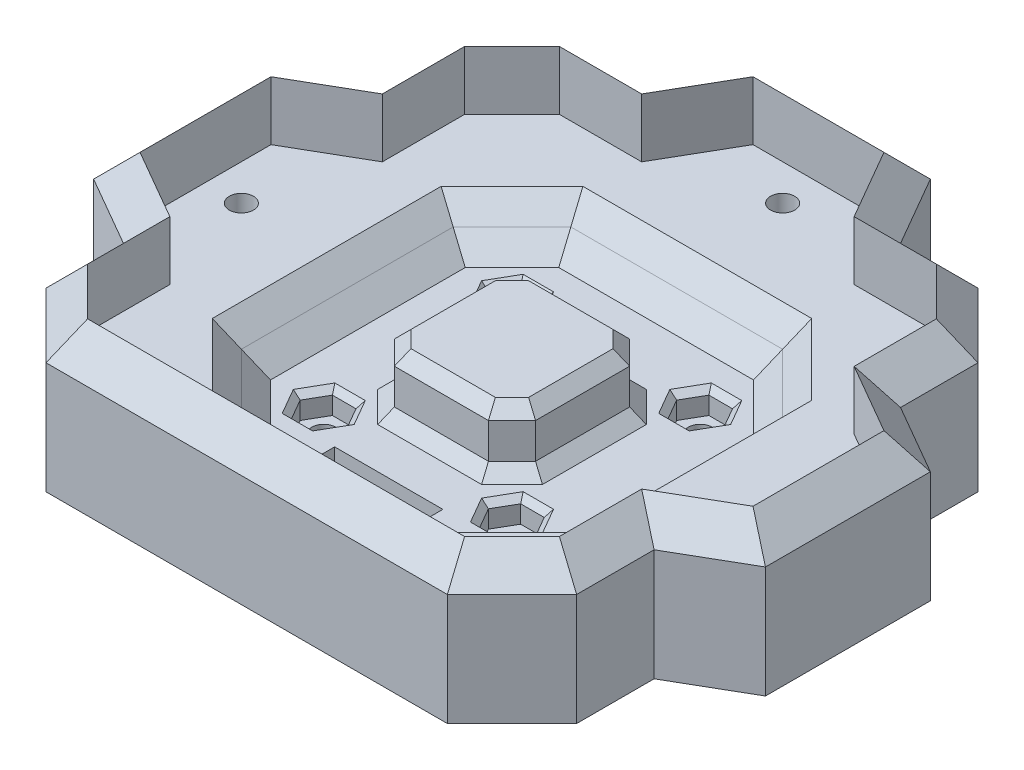
SolidWorks part; units mm, degrees
material "ABS"
ref_plane "Front Plane" through (0, 0, 0) normal (0, 0, 1) x (1, 0, 0)
ref_plane "Top Plane" through (0, 0, 0) normal (0, 1, 0) x (1, 0, 0)
ref_plane "Right Plane" through (0, 0, 0) normal (1, 0, 0) x (0, 0, -1)
sketch "Track Reference" plane through (0, 0, 0) normal (0, 1, 0) x (1, 0, 0)
  line L0 (-40, 32) -> (-32, 40)
  line L1 (-32, 40) -> (-18, 40)
  line L2 (-40, 32) -> (-40, 18)
  line L3 (-32, -40) -> (-5, -40)
  line L4 (40, 32) -> (40, 18)
  line L5 (-40, -32) -> (-32, -40)
  line L6 (32, -40) -> (40, -32)
  line L7 (32, 40) -> (40, 32)
  line L8 (-40, -18) -> (-52, -11.0718)
  line L9 (-52, -11.0718) -> (-52, 11.0718)
  line L10 (-52, 11.0718) -> (-40, 18)
  line L11 (-18, 40) -> (-11.0718, 52)
  line L12 (-11.0718, 52) -> (11.0718, 52)
  line L13 (11.0718, 52) -> (18, 40)
  line L14 (40, 18) -> (52, 11.0718)
  line L15 (52, 11.0718) -> (52, -11.0718)
  line L16 (52, -11.0718) -> (40, -18)
  line L17 (18, -40) -> (11.0718, -52)
  line L18 (11.0718, -52) -> (-11.0718, -52)
  line L19 (-11.0718, -52) -> (-18, -40)
  line L20 (-5, -27.65) -> (-5, -40)
  line L21 (-5, -27.65) -> (-9, -23.65)
  line L22 (-9, -23.65) -> (-9, -21.15)
  line L23 (-9, -21.15) -> (9, -21.15)
  line L24 (9, -21.15) -> (9, -23.65)
  line L25 (9, -23.65) -> (5, -27.65)
  line L26 (5, -27.65) -> (5, -40)
  line L27 (-40, 18) -> (-40, -18) construction
  line L28 (-40, -18) -> (-40, -32)
  line L29 (-18, 40) -> (18, 40) construction
  line L30 (18, 40) -> (32, 40)
  line L31 (40, 18) -> (40, -18) construction
  line L32 (40, -18) -> (40, -32)
  line L33 (-5, -40) -> (5, -40) construction
  line L34 (5, -40) -> (32, -40)
  circle A0 centre (-46, 0) radius 2.05
  circle A1 centre (0, 46) radius 2.05
  circle A2 centre (46, 0) radius 2.05
  circle A3 centre (0, -46) radius 2.05
  point P0 (-40, 40)
  point P1 (40, -40)
  point P2 (-40, -40)
  point P3 (40, 40)
  point P14 (-52, 0)
  point P22 (0, -21.15)
  point P23 (0, 0)
  point P44 (0, 0)
  dimension "D8" = 4.1
  dimension "D1" = 80
  dimension "D2" = 80
  dimension "D3" = 8
  dimension "D4" = 8
  dimension "D5" = 60
  dimension "D6" = 12
  dimension "D7" = 36
  dimension "D9" = 6
  dimension "D12" = 18
  dimension "D11" = 10
  dimension "D13" = 2.5
  dimension "D14" = 45
  dimension "D15" = 18.85
  dimension "D10" = 4
sketch "Sketch2" plane through (0, 0, 0) normal (0, 1, 0) x (1, 0, 0)
  line L127 (-5, -40.1) -> (5, -40.1)
  line L128 (-5, -45.1) -> (5, -45.1)
  line L129 (5, -45.1) -> (34.1125, -45.1)
  line L130 (34.1125, -45.1) -> (45.1, -34.1125)
  line L131 (45.1, -34.1125) -> (45.1, -20.9445)
  line L132 (45.1, -20.9445) -> (57.1, -14.0163)
  line L133 (57.1, -14.0163) -> (57.1, 14.0163)
  line L134 (57.1, 14.0163) -> (45.1, 20.9445)
  line L135 (45.1, 20.9445) -> (45.1, 34.1125)
  line L136 (45.1, 34.1125) -> (34.1125, 45.1)
  line L137 (34.1125, 45.1) -> (20.9445, 45.1)
  line L138 (20.9445, 45.1) -> (14.0163, 57.1)
  line L139 (14.0163, 57.1) -> (-14.0163, 57.1)
  line L140 (-14.0163, 57.1) -> (-20.9445, 45.1)
  line L141 (-20.9445, 45.1) -> (-34.1125, 45.1)
  line L142 (-34.1125, 45.1) -> (-45.1, 34.1125)
  line L143 (-45.1, 34.1125) -> (-45.1, 20.9445)
  line L144 (-45.1, 20.9445) -> (-57.1, 14.0163)
  line L145 (-57.1, 14.0163) -> (-57.1, -14.0163)
  line L146 (-57.1, -14.0163) -> (-45.1, -20.9445)
  line L147 (-45.1, -20.9445) -> (-45.1, -34.1125)
  line L148 (11.1295, 52.1) -> (-11.1295, 52.1)
  line L149 (18.0577, 40.1) -> (11.1295, 52.1)
  line L150 (32.0414, 40.1) -> (18.0577, 40.1)
  line L151 (40.1, 32.0414) -> (32.0414, 40.1)
  line L152 (40.1, 18.0577) -> (40.1, 32.0414)
  line L153 (52.1, 11.1295) -> (40.1, 18.0577)
  line L154 (52.1, -11.1295) -> (52.1, 11.1295)
  line L155 (40.1, -18.0577) -> (52.1, -11.1295)
  line L156 (40.1, -32.0414) -> (40.1, -18.0577)
  line L157 (32.0414, -40.1) -> (40.1, -32.0414)
  line L158 (5, -40.1) -> (32.0414, -40.1)
  line L159 (-32.0414, -40.1) -> (-5, -40.1)
  line L160 (-40.1, -32.0414) -> (-32.0414, -40.1)
  line L161 (-40.1, -18.0577) -> (-40.1, -32.0414)
  line L162 (-52.1, -11.1295) -> (-40.1, -18.0577)
  line L163 (-52.1, 11.1295) -> (-52.1, -11.1295)
  line L164 (-40.1, 18.0577) -> (-52.1, 11.1295)
  line L165 (-40.1, 32.0414) -> (-40.1, 18.0577)
  line L166 (-32.0414, 40.1) -> (-40.1, 32.0414)
  line L167 (-18.0577, 40.1) -> (-32.0414, 40.1)
  line L168 (-11.1295, 52.1) -> (-18.0577, 40.1)
  line L169 (11.1295, 52.1) -> (-11.1295, 52.1)
  line L170 (18.0577, 40.1) -> (11.1295, 52.1)
  line L171 (32.0414, 40.1) -> (18.0577, 40.1)
  line L172 (40.1, 32.0414) -> (32.0414, 40.1)
  line L173 (40.1, 18.0577) -> (40.1, 32.0414)
  line L174 (52.1, 11.1295) -> (40.1, 18.0577)
  line L175 (52.1, -11.1295) -> (52.1, 11.1295)
  line L176 (40.1, -18.0577) -> (52.1, -11.1295)
  line L177 (40.1, -32.0414) -> (40.1, -18.0577)
  line L178 (32.0414, -40.1) -> (40.1, -32.0414)
  line L179 (5, -40.1) -> (32.0414, -40.1)
  line L180 (-32.0414, -40.1) -> (-5, -40.1)
  line L181 (-40.1, -32.0414) -> (-32.0414, -40.1)
  line L182 (-40.1, -18.0577) -> (-40.1, -32.0414)
  line L183 (-52.1, -11.1295) -> (-40.1, -18.0577)
  line L184 (-52.1, 11.1295) -> (-52.1, -11.1295)
  line L185 (-40.1, 18.0577) -> (-52.1, 11.1295)
  line L186 (-40.1, 32.0414) -> (-40.1, 18.0577)
  line L187 (-32.0414, 40.1) -> (-40.1, 32.0414)
  line L188 (-18.0577, 40.1) -> (-32.0414, 40.1)
  line L189 (-11.1295, 52.1) -> (-18.0577, 40.1)
  line L190 (-45.1, -34.1125) -> (-34.1125, -45.1)
  line L191 (-34.1125, -45.1) -> (-5, -45.1)
  dimension "D1" = 0.1
  dimension "D2" = 5
extrude "Outer Walls Extrude" add sketch "Sketch2" along normal blind 10
sketch "Sketch3" plane through (0, 0, 0) normal (0, -1, 0) x (1, 0, 0)
  line L20 (34.1125, 45.1) -> (-34.1125, 45.1)
  line L21 (-34.1125, 45.1) -> (-45.1, 34.1125)
  line L22 (-45.1, 34.1125) -> (-45.1, 20.9445)
  line L23 (-45.1, 20.9445) -> (-57.1, 14.0163)
  line L24 (-57.1, 14.0163) -> (-57.1, -14.0163)
  line L25 (-57.1, -14.0163) -> (-45.1, -20.9445)
  line L26 (-45.1, -20.9445) -> (-45.1, -34.1125)
  line L27 (-45.1, -34.1125) -> (-34.1125, -45.1)
  line L28 (-34.1125, -45.1) -> (-20.9445, -45.1)
  line L29 (-20.9445, -45.1) -> (-14.0163, -57.1)
  line L30 (-14.0163, -57.1) -> (14.0163, -57.1)
  line L31 (14.0163, -57.1) -> (20.9445, -45.1)
  line L32 (20.9445, -45.1) -> (34.1125, -45.1)
  line L33 (34.1125, -45.1) -> (45.1, -34.1125)
  line L34 (45.1, -34.1125) -> (45.1, -20.9445)
  line L35 (45.1, -20.9445) -> (57.1, -14.0163)
  line L36 (57.1, -14.0163) -> (57.1, 14.0163)
  line L37 (57.1, 14.0163) -> (45.1, 20.9445)
  line L38 (45.1, 20.9445) -> (45.1, 34.1125)
  line L39 (45.1, 34.1125) -> (34.1125, 45.1)
  line L40 (34.1125, 45.1) -> (-34.1125, 45.1)
  line L41 (-34.1125, 45.1) -> (-45.1, 34.1125)
  line L42 (-45.1, 34.1125) -> (-45.1, 20.9445)
  line L43 (-45.1, 20.9445) -> (-57.1, 14.0163)
  line L44 (-57.1, 14.0163) -> (-57.1, -14.0163)
  line L45 (-57.1, -14.0163) -> (-45.1, -20.9445)
  line L46 (-45.1, -20.9445) -> (-45.1, -34.1125)
  line L47 (-45.1, -34.1125) -> (-34.1125, -45.1)
  line L48 (-34.1125, -45.1) -> (-20.9445, -45.1)
  line L49 (-20.9445, -45.1) -> (-14.0163, -57.1)
  line L50 (-14.0163, -57.1) -> (14.0163, -57.1)
  line L51 (14.0163, -57.1) -> (20.9445, -45.1)
  line L52 (20.9445, -45.1) -> (34.1125, -45.1)
  line L53 (34.1125, -45.1) -> (45.1, -34.1125)
  line L54 (45.1, -34.1125) -> (45.1, -20.9445)
  line L55 (45.1, -20.9445) -> (57.1, -14.0163)
  line L56 (57.1, -14.0163) -> (57.1, 14.0163)
  line L57 (57.1, 14.0163) -> (45.1, 20.9445)
  line L58 (45.1, 20.9445) -> (45.1, 34.1125)
  line L59 (45.1, 34.1125) -> (34.1125, 45.1)
  dimension "D1" = 0
extrude "Base Extrude" add sketch "Sketch3" along normal blind 14
sketch "Sketch11" plane through (0, 0, 0) normal (0, 1, 0) x (1, 0, 0)
  line L15 (-5.2, -40) -> (-5.2, -40.1)
  line L16 (-32.0414, -40.1) -> (32.0414, -40.1) construction
  line L17 (5.2, -40) -> (5.2, -40.1)
  line L18 (5.2, -40.1) -> (-5.2, -40.1)
  line L22 (5.2, -40) -> (5.2, -27.7328)
  line L23 (5.2, -27.7328) -> (9.2, -23.7328)
  line L24 (9.2, -23.7328) -> (9.2, -20.95)
  line L25 (9.2, -20.95) -> (-9.2, -20.95)
  line L26 (-9.2, -20.95) -> (-9.2, -23.7328)
  line L27 (-9.2, -23.7328) -> (-5.2, -27.7328)
  line L28 (-5.2, -27.7328) -> (-5.2, -40)
  line L29 (5.2, -40) -> (5.2, -27.7328)
  line L30 (5.2, -27.7328) -> (9.2, -23.7328)
  line L31 (9.2, -23.7328) -> (9.2, -20.95)
  line L32 (9.2, -20.95) -> (-9.2, -20.95)
  line L33 (-9.2, -20.95) -> (-9.2, -23.7328)
  line L34 (-9.2, -23.7328) -> (-5.2, -27.7328)
  line L35 (-5.2, -27.7328) -> (-5.2, -40)
  dimension "D1" = 0.2
extrude "Rack Cut" cut sketch "Sketch11" against normal through all
chamfer "Walls Outer Chamfer" distance 5 angle 45 20 edges at (-39.6062, 10, 39.6062) (-45.1, 10, 27.5285) (-51.1, 10, 17.4804) (0, 10, 45.1) (39.6062, 10, 39.6062) (45.1, 10, 27.5285) (51.1, 10, 17.4804) (57.1, 10, 0) (51.1, 10, -17.4804) (45.1, 10, -27.5285) (39.6062, 10, -39.6062) (27.5285, 10, -45.1) (17.4804, 10, -51.1) (0, 10, -57.1) (-17.4804, 10, -51.1) (-27.5285, 10, -45.1) (-39.6062, 10, -39.6062) (-45.1, 10, -27.5285) (-51.1, 10, -17.4804) (-57.1, 10, 0)
sketch "Sketch6" plane through (0, 0, 0) normal (0, 1, 0) x (1, 0, 0)
  line L1 (18, -28) -> (-18, -28)
  line L2 (28, -18) -> (28, 18)
  line L3 (18, 28) -> (-18, 28)
  line L4 (-28, -18) -> (-28, 18)
  line L5 (-18, 28) -> (-28, 18)
  line L6 (-18, -28) -> (-28, -18)
  line L7 (28, -18) -> (18, -28)
  line L8 (28, 18) -> (18, 28)
  point P0 (0, 0)
  point P1 (-28, 0)
  point P15 (0, 28)
  dimension "D1" = 56
  dimension "D2" = 10
extrude "Spacer Cutout" cut sketch "Sketch6" against normal offset from surface (7 mm away) 7 up to face at (0, -14, 28.1289)
chamfer "Spacer Chamfer" distance 3.5 angle 45 18 edges at (11.6, -7, 28) (23, -7, 23) (28, -7, 0) (23, -7, -23) (0, -7, -28) (-11.6, -7, 28) (-23, -7, 23) (-28, -7, 0) (-23, -7, -23) (28, 0, 0) (23, 0, -23) (0, 0, -28) (23, 0, 23) (11.6, 0, 28) (-11.6, 0, 28) (-23, 0, 23) (-28, 0, 0) (-23, 0, -23)
sketch "Sketch12" plane through (0, -7, 0) normal (0, 1, 0) x (1, 0, 0)
  line L0 (-12, 8) -> (-8, 12)
  line L1 (-8, -12) -> (8, -12)
  line L2 (-12, -8) -> (-12, 8)
  line L3 (-8, 12) -> (8, 12)
  line L4 (12, -8) -> (12, 8)
  line L7 (-12, -8) -> (-8, -12)
  line L8 (8, -12) -> (12, -8)
  line L9 (8, 12) -> (12, 8)
  point P0 (0, 0)
  point P3 (0, 12)
  point P4 (-12, 0)
  dimension "D1" = 24
  dimension "D2" = 4
extrude "Bumper Extrude" add sketch "Sketch12" along normal blind 10
chamfer "Bumper Chamfer" distance 2 angle 45 16 edges at (-10, 3, -10) (0, 3, -12) (10, 3, -10) (12, 3, 0) (10, 3, 10) (0, 3, 12) (-10, 3, 10) (-12, 3, 0) (-10, -7, -10) (0, -7, -12) (10, -7, -10) (12, -7, 0) (10, -7, 10) (0, -7, 12) (-12, -7, 0) (-10, -7, 10)
sketch "Sketch5" plane through (0, 0, 0) normal (0, 1, 0) x (1, 0, 0)
  circle A0 centre (46, 0) radius 2.05 construction
  circle A1 centre (0, 46) radius 2.05 construction
  circle A2 centre (-46, 0) radius 2.05 construction
  circle A3 centre (46, 0) radius 2.05
  circle A4 centre (0, 46) radius 2.05
  circle A5 centre (-46, 0) radius 2.05
extrude "Track Mount Holes" cut sketch "Sketch5" against normal through all
sketch "Sketch10" plane through (0, -14, 0) normal (0, -1, 0) x (1, 0, 0)
  circle A0 centre (-46, 0) radius 3.5
  circle A1 centre (0, -46) radius 3.5
  circle A2 centre (46, 0) radius 3.5
  dimension "D1" = 7
extrude "Track Mount Countersink" cut sketch "Sketch10" against normal blind 3
chamfer "Track Mount Countersink Chamfer" distance 1.5 angle 45 6 edges at (46, -14, -3.5) (0, -14, -49.5) (-46, -14, -3.5) (46, -11, -2.05) (0, -11, -48.05) (-46, -11, -2.05)
sketch "Sketch7" plane through (0, -7, 0) normal (0, 1, 0) x (1, 0, 0)
  line L1 (16, -16) -> (-16, -16) construction
  line L2 (16, -16) -> (16, 16) construction
  line L3 (16, 16) -> (-16, 16) construction
  line L4 (-16, -16) -> (-16, 16) construction
  line L5 (16, -16) -> (-16, 16) construction
  line L6 (16, 16) -> (-16, -16) construction
  circle A0 centre (-16, 16) radius 2.05
  circle A1 centre (16, 16) radius 2.05
  circle A2 centre (16, -16) radius 2.05
  circle A3 centre (-16, -16) radius 2.05
  point P0 (0, 0)
  dimension "D2" = 4.1
  dimension "D1" = 32
extrude "Floor Mount Holes" cut sketch "Sketch7" against normal through all
sketch "Sketch9" plane through (0, -7, 0) normal (0, 1, 0) x (1, 0, 0)
  line L1 (-11.9874, 16) -> (-13.9937, 19.475)
  line L2 (-13.9937, 19.475) -> (-18.0063, 19.475)
  line L3 (-18.0063, 19.475) -> (-20.0126, 16)
  line L4 (-20.0126, 16) -> (-18.0063, 12.525)
  line L5 (-18.0063, 12.525) -> (-13.9937, 12.525)
  line L6 (-13.9937, 12.525) -> (-11.9874, 16)
  line L7 (11.9874, 16) -> (13.9937, 12.525)
  line L8 (13.9937, 12.525) -> (18.0063, 12.525)
  line L9 (18.0063, 12.525) -> (20.0126, 16)
  line L10 (20.0126, 16) -> (18.0063, 19.475)
  line L11 (18.0063, 19.475) -> (13.9937, 19.475)
  line L12 (13.9937, 19.475) -> (11.9874, 16)
  line L13 (-11.9874, -16) -> (-13.9937, -12.525)
  line L14 (-13.9937, -12.525) -> (-18.0063, -12.525)
  line L15 (-18.0063, -12.525) -> (-20.0126, -16)
  line L16 (-20.0126, -16) -> (-18.0063, -19.475)
  line L17 (-18.0063, -19.475) -> (-13.9937, -19.475)
  line L18 (-13.9937, -19.475) -> (-11.9874, -16)
  line L19 (11.9874, -16) -> (13.9937, -19.475)
  line L20 (13.9937, -19.475) -> (18.0063, -19.475)
  line L21 (18.0063, -19.475) -> (20.0126, -16)
  line L22 (20.0126, -16) -> (18.0063, -12.525)
  line L23 (18.0063, -12.525) -> (13.9937, -12.525)
  line L24 (13.9937, -12.525) -> (11.9874, -16)
  circle A0 centre (-16, 16) radius 3.475 construction
  circle A1 centre (16, 16) radius 3.475 construction
  circle A2 centre (-16, -16) radius 3.475 construction
  circle A3 centre (16, -16) radius 3.475 construction
  dimension "D1" = 6.95
extrude "Floor Mount Nut Inset" cut sketch "Sketch9" against normal blind 4
chamfer "Floor Mount Nut Chamfer" distance 1 angle 45 24 edges at (16, -7, 19.475) (19.0094, -7, 17.7375) (19.0094, -7, 14.2625) (12.9906, -7, 17.7375) (12.9906, -7, 14.2625) (16, -7, 12.525) (-19.0094, -7, 14.2625) (-19.0094, -7, 17.7375) (-16, -7, 19.475) (-12.9906, -7, 17.7375) (-12.9906, -7, 14.2625) (-16, -7, 12.525) (16, -7, -12.525) (19.0094, -7, -14.2625) (19.0094, -7, -17.7375) (12.9906, -7, -14.2625) (12.9906, -7, -17.7375) (16, -7, -19.475) (-19.0094, -7, -17.7375) (-19.0094, -7, -14.2625) (-16, -7, -12.525) (-12.9906, -7, -14.2625) (-12.9906, -7, -17.7375) (-16, -7, -19.475)
equation "\"D2@Track Reference\"=\"D1@Track Reference\""
